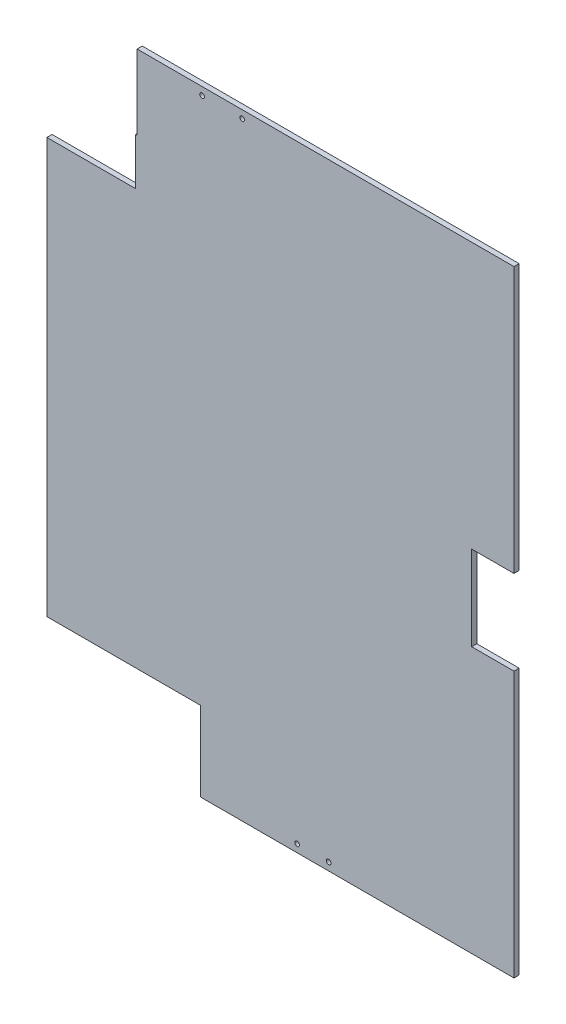
SolidWorks part; units mm, degrees
material "Balsa"
ref_plane "Front Plane" through (0, 0, 0) normal (0, 0, 1) x (1, 0, 0)
ref_plane "Top Plane" through (0, 0, 0) normal (0, 1, 0) x (1, 0, 0)
ref_plane "Right Plane" through (0, 0, 0) normal (1, 0, 0) x (0, 0, -1)
sketch "Sketch1" plane through (0, 0, 0) normal (0, 0, 1) x (1, 0, 0)
  line L0 (-5.7823, -13) -> (25.5, -13)
  line L2 (-5.7823, 1) -> (-5.7823, -13)
  line L5 (24.5, -14) -> (-24.5, -14) construction
  line L6 (323.7481, -265) -> (323.7481, 30)
  line L7 (-5.8246, -265) -> (65.6329, -265)
  line L8 (-5.8246, -265) -> (-5.8246, -225)
  line L11 (-5.8246, -265) -> (65.6329, -225) construction
  line L12 (-5.8246, -225) -> (65.6329, -265) construction
  line L15 (323.7481, -265) -> (25.5, -265)
  line L16 (25.5, 1) -> (25.5, -265)
  line L17 (-5.8246, -225) -> (25.5, -225)
  line L18 (-24.5, -224) -> (24.5, -224) construction
  line L19 (-5.7823, 1) -> (25.5, 1)
  line L20 (24.5, -224) -> (24.5, -14) construction
  line L21 (-85.1981, 31) -> (50.7481, 31) construction
  line L23 (25.5, 1) -> (25.5, 30)
  line L24 (25.5, 30) -> (323.7481, 30)
  line L27 (277.3251, 57) -> (277.3251, -295) construction
  line L28 (26.2777, -266) -> (-26.2882, -266) construction
  line L30 (-63.4467, 81) -> (255.5737, 81) construction
  line L31 (83.0863, 30) -> (323.7481, 30)
  line L32 (83.0863, 30) -> (83.0863, 77.7)
  line L33 (83.0863, 77.7) -> (323.7481, 77.7)
  line L34 (323.7481, 30) -> (323.7481, 77.7)
  line L35 (83.0863, 30) -> (323.7481, 77.7) construction
  line L36 (83.0863, 77.7) -> (323.7481, 30) construction
  line L37 (255.5737, -319) -> (-63.4467, -319) construction
  line L38 (323.7481, -265) -> (123.7481, -265)
  line L39 (323.7481, -265) -> (323.7481, -315.7)
  line L40 (323.7481, -315.7) -> (123.7481, -315.7)
  line L41 (123.7481, -265) -> (123.7481, -315.7)
  line L42 (323.7481, -265) -> (123.7481, -315.7) construction
  line L43 (323.7481, -315.7) -> (123.7481, -265) construction
  line L44 (50.7481, 31) -> (50.7481, -269) construction
  line L45 (83.0863, 31) -> (83.0863, -269) construction
  point P4 (32.4695, -6)
  point P10 (29.9042, -245)
  point P15 (48.1318, -132)
  point P24 (48.1318, 15.5)
  point P36 (203.4172, 53.85)
  point P42 (223.7481, -290.35)
  dimension "D1" = 1
  dimension "D2" = 1
  dimension "D3" = 1
  dimension "D4" = 1
  dimension "D5" = 1
  dimension "D6" = 31.3246
  dimension "D7" = 273
  dimension "D8" = 3.3
  dimension "D9" = 200
  dimension "D10" = 3.3
extrude "Boss-Extrude1" add sketch "Sketch1" along normal blind 3.3 contours L24 L23 L16 L7 L15 L6 | L15 L41 L40 L39 | L24 L34 L33 L32 region at (174.6241, -117.5, 0) region at (203.4172, 53.85, 0) region at (223.7481, -290.35, 0)
sketch "Sketch2" plane through (0, 0, 0) normal (0, 0, -1) x (-1, 0, 0)
  circle A0 centre (-150.2163, 72.7) radius 1.5
  circle A1 centre (-124.6149, 72.7) radius 1.5
  circle A2 centre (-205.3942, -310.7) radius 1.5
  circle A3 centre (-185.3098, -310.7) radius 1.5
  circle A4 centre (-150.2163, 72.7) radius 2 construction
  circle A5 centre (-124.6149, 72.7) radius 2 construction
  circle A6 centre (-205.3942, -310.7) radius 2 construction
  circle A7 centre (-185.3098, -310.7) radius 2 construction
  dimension "D1" = 3
  dimension "D2" = 3
  dimension "D3" = 3
  dimension "D4" = 3
extrude "Cut-Extrude1" cut sketch "Sketch2" against normal through all
sketch "Sketch3" plane through (119.3915, 0, 256.0358) normal (0.4226, 0, 0.9063) x (0.9063, 0, -0.4226)
  line L1 (293.4595, -146) -> (268.9595, -146)
  line L2 (293.4595, -146) -> (293.4595, -92)
  line L3 (293.4595, -92) -> (268.9595, -92)
  line L4 (268.9595, -146) -> (268.9595, -92)
  line L5 (293.4595, -146) -> (268.9595, -92) construction
  line L6 (293.4595, -92) -> (268.9595, -146) construction
  point P4 (281.2095, -119)
extrude "Cut-Extrude2" cut sketch "Sketch3" against normal through all both and the other way through all
sketch "Sketch4" plane through (0, 0, 0) normal (0, 0, -1) x (-1, 0, 0)
  line L1 (-323.7481, -92) -> (-296.7639, -92)
  line L2 (-323.7481, -92) -> (-323.7481, -146)
  line L3 (-323.7481, -146) -> (-296.7639, -146)
  line L4 (-296.7639, -92) -> (-296.7639, -146)
  line L5 (-323.7481, -92) -> (-296.7639, -146) construction
  line L6 (-323.7481, -146) -> (-296.7639, -92) construction
  point P4 (-310.256, -119)
extrude "Cut-Extrude3" cut sketch "Sketch4" against normal blind 10
sketch "Sketch6" plane through (0, 0, 3.3) normal (0, 0, 1) x (1, 0, 0)
  line L1 (25.5, 30) -> (82.2279, 30)
  line L2 (25.5, 30) -> (25.5, 0)
  line L3 (25.5, 0) -> (82.2279, 0)
  line L4 (82.2279, 30) -> (82.2279, 0)
  line L5 (25.5, 30) -> (82.2279, 0) construction
  line L6 (25.5, 0) -> (82.2279, 30) construction
  point P4 (53.864, 15)
extrude "Cut-Extrude4" cut sketch "Sketch6" against normal blind 10
